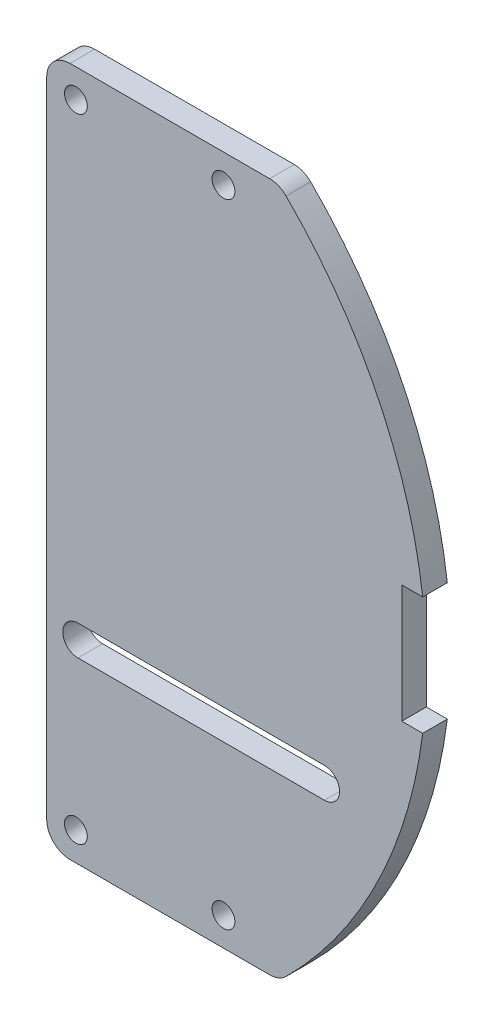
SolidWorks part; units mm, degrees
material "Delrin 2700 NC010, Low Viscosity Acetal Copolymer (SS)"
ref_plane "Front Plane" through (0, 0, 0) normal (0, 0, 1) x (1, 0, 0)
ref_plane "Top Plane" through (0, 0, 0) normal (0, 1, 0) x (1, 0, 0)
ref_plane "Right Plane" through (0, 0, 0) normal (1, 0, 0) x (0, 0, -1)
sketch "Sketch1" plane through (0, 0, 0) normal (0, 0, 1) x (1, 0, 0)
  line L2 (12.5875, 44.5) -> (42.5875, 44.5)
  line L5 (12.5875, -44.5) -> (12.5875, 44.5)
  line L8 (12.5875, -44.5) -> (42.5875, -44.5)
  arc A4 (42.5875, 44.5) -> (42.5875, -44.5) centre (0, 0) cw
  dimension "D2" = 30
extrude "Boss-Extrude1" add sketch "Sketch1" along normal blind 3.175
sketch "Sketch2" plane through (0, 0, 3.175) normal (0, 0, 1) x (1, 0, 0)
  line L0 (12.5875, 0) -> (61.595, 0) construction
  line L1 (12.5875, 44.5) -> (12.5875, -44.5) construction
  circle A0 centre (16.3543, -40.8119) radius 1.4732
  arc A1 (42.5875, -44.5) -> (42.5875, 44.5) centre (0, 0) ccw construction
  circle A2 centre (35.4043, -40.8119) radius 1.4732
  circle A3 centre (16.3543, 40.8119) radius 1.4732
  circle A4 centre (35.4043, 40.8119) radius 1.4732
  dimension "D1" = 2
extrude "Cut-Extrude1" cut sketch "Sketch2" against normal through all
sketch "Sketch3" plane through (0, 0, 3.175) normal (0, 0, 1) x (1, 0, 0)
  line L0 (58.42, 7.62) -> (61.1218, 7.62) construction
  line L1 (58.42, -7.62) -> (61.1218, -7.62) construction
  line L2 (58.42, 7.62) -> (58.42, -7.62) construction
  line L3 (58.42, 7.62) -> (61.1218, 7.62)
  line L4 (58.42, -7.62) -> (61.1218, -7.62)
  line L5 (58.42, 7.62) -> (58.42, -7.62)
  arc A0 (42.5875, -44.5) -> (42.5875, 44.5) centre (0, 0) ccw construction
  arc A1 (61.1218, -7.62) -> (61.1218, 7.62) centre (0, 0) ccw
extrude "Cut-Extrude2" cut sketch "Sketch3" against normal through all
fillet "Fillet1" radius 3 4 edges at (12.5875, -44.5, 1.5875) (42.5875, -44.5, 1.5875) (12.5875, 44.5, 1.5875) (42.5875, 44.5, 1.5875)
sketch "Sketch4" plane through (0, 0, 3.175) normal (0, 0, 1) x (1, 0, 0)
  line L0 (46.9295, -14.42) -> (8.8343, -14.42)
  line L1 (8.8343, -14.42) -> (8.8343, -24.58)
  line L2 (8.8343, -24.58) -> (46.9295, -24.58)
  arc A0 (46.9295, -24.58) -> (46.9295, -14.42) centre (46.9295, -19.5) ccw
extrude "Cut-Extrude3" [suppressed] cut sketch "Sketch4" against normal through all
fillet "Fillet2" [suppressed] radius 3
sketch "Sketch5" plane through (0, 0, 3.175) normal (0, 0, 1) x (1, 0, 0)
  line L0 (16.6122, -19.5) -> (48.4448, -19.5) construction
  line L1 (16.6122, -17.5542) -> (48.4448, -17.5542)
  line L2 (16.6122, -21.4458) -> (48.4448, -21.4458)
  arc A0 (16.6122, -17.5542) -> (16.6122, -21.4458) centre (16.6122, -19.5) ccw
  circle A2 centre (45.3296, -19.5) radius 4.318 construction
  arc A3 (48.4448, -21.4458) -> (48.4448, -17.5542) centre (48.4448, -19.5) ccw
  arc A4 (49.2918, -21.2165) -> (51.8682, -13.8285) centre (-1.4274, 0.6141) ccw construction
  arc A5 (15.5478, -26.4804) -> (48.4448, -23.6057) centre (12.5875, 197.0625) ccw construction
  point P12 (32.5285, -19.5)
  dimension "D1" = 8.636
  dimension "D2" = 31.8326
  dimension "D3" = 3.8915
extrude "Cut-Extrude5" cut sketch "Sketch5" against normal through all
